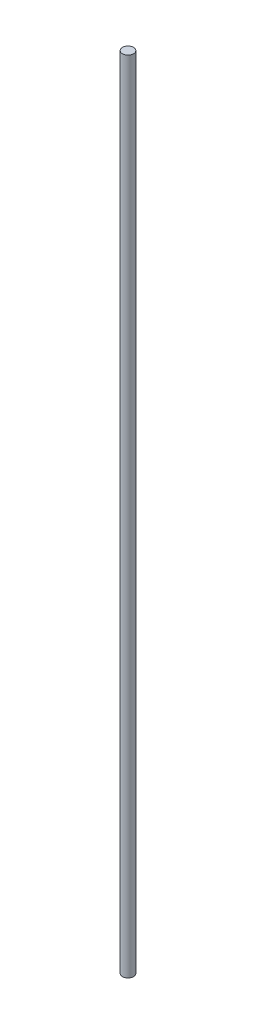
SolidWorks part; units mm, degrees
ref_plane "Front Plane" through (0, 0, 0) normal (0, 0, 1) x (1, 0, 0)
ref_plane "Top Plane" through (0, 0, 0) normal (0, 1, 0) x (1, 0, 0)
ref_plane "Right Plane" through (0, 0, 0) normal (1, 0, 0) x (0, 0, -1)
sketch "Sketch1" plane through (0, 0, 0) normal (0, 1, 0) x (1, 0, 0)
  circle A0 centre (0, 0) radius 6.35
  dimension "D1" = 12.7
extrude "Boss-Extrude1" add sketch "Sketch1" along normal blind 914.4
